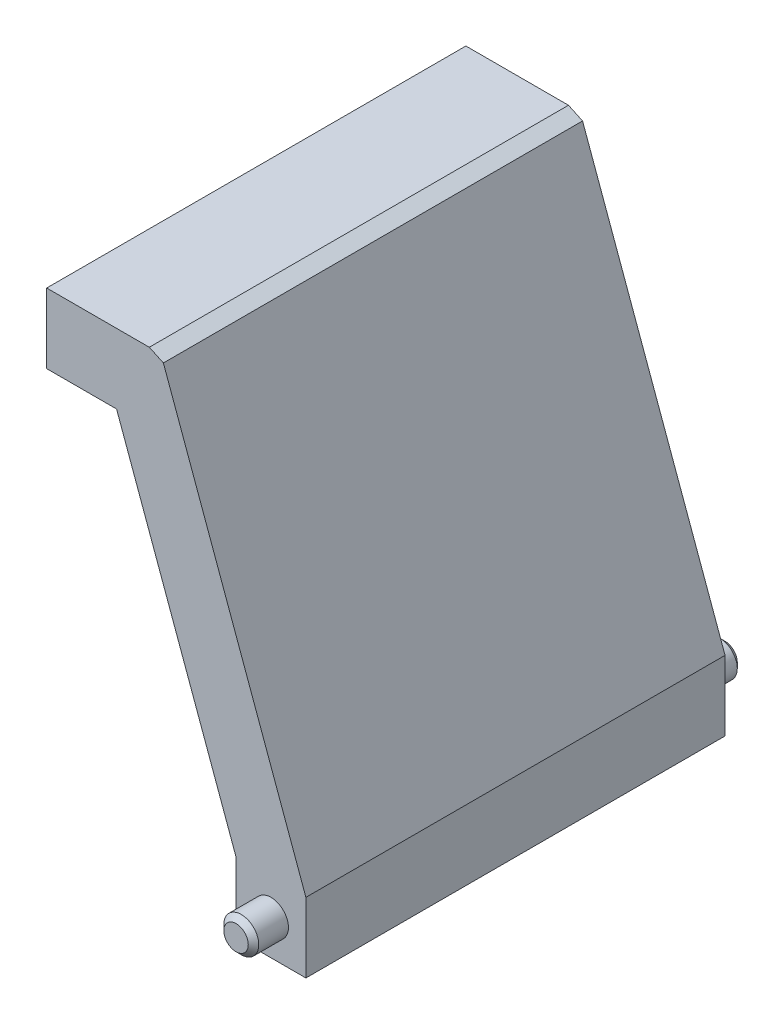
SolidWorks part; units mm, degrees
ref_plane "Front Plane" through (0, 0, 0) normal (0, 0, 1) x (1, 0, 0)
ref_plane "Top Plane" through (0, 0, 0) normal (0, 1, 0) x (1, 0, 0)
ref_plane "Right Plane" through (0, 0, 0) normal (1, 0, 0) x (0, 0, -1)
sketch "Sketch1" plane through (0, 0, 0) normal (0, 0, 1) x (1, 0, 0)
  line L0 (-5, 5) -> (-22.101, 51.9846)
  line L1 (-5, -5) -> (5, -5)
  line L2 (-5, -5) -> (-5, 5)
  line L3 (-5, 5) -> (5, 5)
  line L4 (5, -5) -> (5, 5)
  line L5 (-5, -5) -> (5, 5) construction
  line L6 (-5, 5) -> (5, -5) construction
  line L7 (5, 5) -> (-12.101, 51.9846)
  line L8 (-12.101, 51.9846) -> (-15.7407, 61.9846)
  line L9 (-22.101, 51.9846) -> (-32.101, 51.9846)
  line L10 (-22.101, 51.9846) -> (-22.101, 61.9846)
  line L11 (-22.101, 61.9846) -> (-32.101, 61.9846)
  line L12 (-32.101, 51.9846) -> (-32.101, 61.9846)
  line L13 (-15.7407, 61.9846) -> (-22.101, 61.9846)
  point P0 (0, 0)
  dimension "D1" = 10
  dimension "D2" = 10
  dimension "D3" = 10
  dimension "D4" = 10
extrude "Boss-Extrude1" add sketch "Sketch1" along normal blind 60 contours L12 L9 L10 L11 | L8 L13 L10 L0 L3 L7 | L1 L4 L3 L2 region at (0, 0, 0) region at (-9.9433, 32.6623, 0) region at (-27.101, 56.9846, 0)
chamfer "Chamfer1" distance 3 angle 45 1 edges at (-5, -5, 30)
sketch "Sketch2" plane through (0, 0, 60) normal (0, 0, 1) x (1, 0, 0)
  circle A0 centre (0, 0) radius 2.5
extrude "Boss-Extrude2" add sketch "Sketch2" along normal blind 5 from surface starting at face at (-11.5604, 25.1043, 60)
extrude "Boss-Extrude3" add sketch "Sketch2<2>" against normal blind 5 from surface contours A0 starting at face at (-11.5604, 25.1043, 0)
sketch "Sketch2<2>" plane through (0, 0, 60) normal (0, 0, 1) x (1, 0, 0) same geometry as "Sketch2"
chamfer "Chamfer2" distance 1 angle 45 1 edges at (-15.7407, 61.9846, 30) first distance on face at (-5.3704, 33.4923, 30)
chamfer "Chamfer3" distance 0.75 angle 45 2 edges at (2.5, 0, -5) (2.5, 0, 65)
